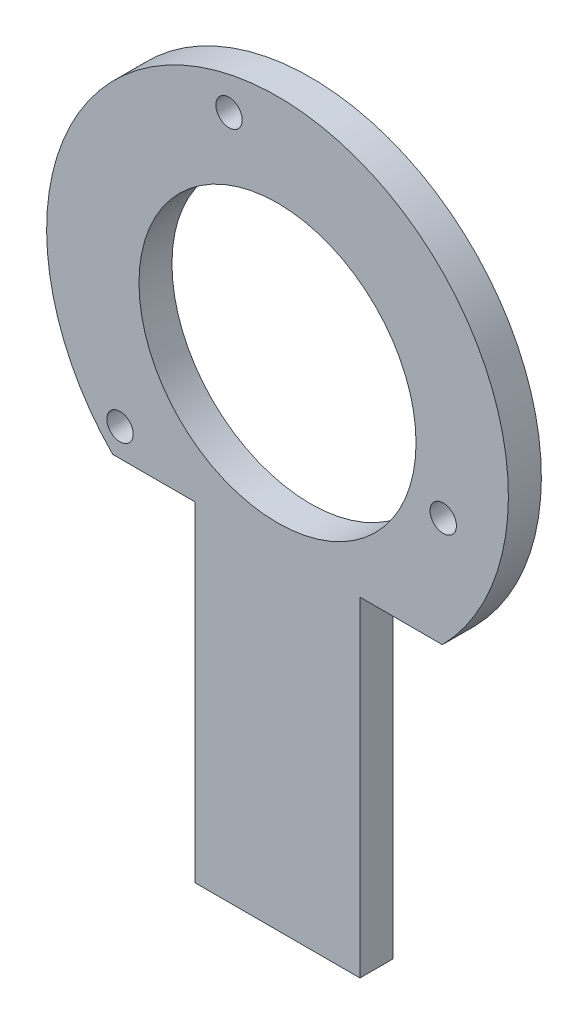
SolidWorks part; units mm, degrees
ref_plane "Front Plane" through (0, 0, 0) normal (0, 0, 1) x (1, 0, 0)
ref_plane "Top Plane" through (0, 0, 0) normal (0, 1, 0) x (1, 0, 0)
ref_plane "Right Plane" through (0, 0, 0) normal (1, 0, 0) x (0, 0, -1)
sketch "Sketch1" plane through (0, 0, 0) normal (0, 0, 1) x (1, 0, 0)
  circle A0 centre (0, 0) radius 35.56
  dimension "D1" = 71.12
extrude "Boss-Extrude1" add sketch "Sketch1" along normal blind 5.08
sketch "Sketch2" plane through (0, 0, 5.08) normal (0, 0, 1) x (1, 0, 0)
  line L0 (0, 0) -> (0, -35.56) construction
  line L6 (0, -35.56) -> (-36.2561, -35.56)
  line L7 (-36.2561, -35.56) -> (-36.2561, -24.892)
  line L8 (-36.2561, -24.892) -> (33.7504, -24.892)
  line L9 (33.7504, -24.892) -> (33.7504, -35.56)
  line L10 (33.7504, -35.56) -> (0, -35.56)
  circle A0 centre (0, 0) radius 35.56 construction
  dimension "D1" = 10.668
extrude "Cut-Extrude1" cut sketch "Sketch2" against normal through all
ref_axis "Axis1" through (0, -24.892, 0) along (0, 0, 1)
ref_plane "Plane1" through (0, 0, 0) normal (1, 0, 0) x (0, 0, 1)
sketch "Sketch7" plane through (0, 0, 5.08) normal (0, 0, 1) x (1, 0, 0)
  line L0 (-7.472, 29.6655) -> (-24.2611, -20.6265) construction
  line L1 (-7.472, 29.6655) -> (25.5229, -7.9528) construction
  line L2 (25.5229, -7.9528) -> (-24.2611, -20.6265) construction
  circle A0 centre (-24.2611, -20.6265) radius 2.032
  circle A1 centre (-7.472, 29.6655) radius 2.032
  circle A2 centre (25.5229, -7.9528) radius 2.032
  dimension "D1" = 4.064
  dimension "D2" = 50.292
  dimension "D3" = 50.038
  dimension "D4" = 49.784
extrude "Cut-Extrude2" cut sketch "Sketch7" against normal through all
sketch "Sketch8" plane through (0, 0, 0) normal (0, 0, -1) x (-1, 0, 0)
  circle A0 centre (0, 0) radius 21.336
  dimension "D1" = 42.672
extrude "Cut-Extrude3" cut sketch "Sketch8" against normal through all
sketch "Sketch9" plane through (0, -24.892, 0) normal (0, -1, 0) x (1, 0, 0)
  line L0 (0, 5.08) -> (0, 0) construction
  line L1 (25.3949, 5.08) -> (-25.3949, 5.08) construction
  line L3 (-12.7, 0) -> (12.7, 0)
  line L4 (-12.7, 0) -> (-12.7, 5.08)
  line L5 (-12.7, 5.08) -> (12.7, 5.08)
  line L6 (12.7, 0) -> (12.7, 5.08)
  line L7 (-12.7, 0) -> (12.7, 5.08) construction
  line L8 (-12.7, 5.08) -> (12.7, 0) construction
  point P5 (0, 2.54)
  dimension "D2" = 5.08
extrude "Boss-Extrude2" add sketch "Sketch9" along normal blind 50.8
equation "\"Foamcore\" = .1in"
equation "\"MDF\" = .2in"
equation "\"Gmaterial\"= \"MDF\""
equation "\"PVC-ID\" = \"1.590in\""
equation "\"PVC-OD\" = \"1.900in\""
equation "\"PVC-Sleeve-Width\" = \".51in\""
equation "\"D1@Boss-Extrude1\"=\"Gmaterial\""
equation "\"D2@Sketch9\"=\"Gmaterial\""
